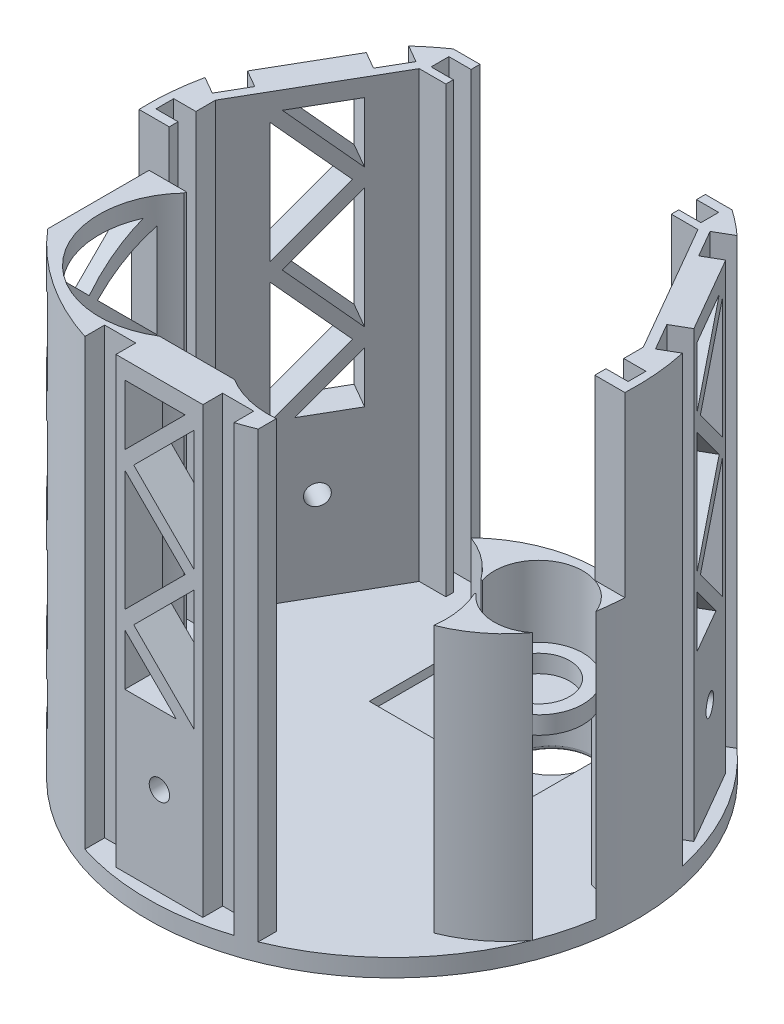
SolidWorks part; units mm, degrees
material "AISI Type 316L stainless steel"
ref_plane "Front Plane" through (0, 0, 0) normal (0, 0, 1) x (1, 0, 0)
ref_plane "Top Plane" through (0, 0, 0) normal (0, 1, 0) x (1, 0, 0)
ref_plane "Right Plane" through (0, 0, 0) normal (1, 0, 0) x (0, 0, -1)
other "Center of Mass"
sketch "Sketch1" plane through (0, 0, 0) normal (0, 1, 0) x (1, 0, 0)
  line L0 (0, 0) -> (0, -30.5) construction
  line L1 (-7.894, -24.4607) -> (-5.394, -24.4607)
  line L2 (0, 0) -> (-7.894, -29.4607) construction
  line L3 (-7.894, -29.4607) -> (7.894, -29.4607) construction
  line L4 (7.894, -29.4607) -> (7.894, -24.4607)
  line L5 (-7.894, -29.4607) -> (-7.894, -24.4607)
  line L6 (7.894, -24.4607) -> (5.394, -24.4607)
  line L7 (-5.394, -24.4607) -> (-5.394, -27.9849)
  line L8 (-8.394, -26.1876) -> (8.394, -26.1876) construction
  line L9 (5.394, -27.9849) -> (5.394, -24.4607)
  line L10 (5.394, -24.4607) -> (5.5317, -24.5711)
  line L11 (-8.394, -26.1876) -> (-8.394, -23.9607)
  line L12 (-8.394, -23.9607) -> (-4.894, -23.9607)
  line L13 (-4.894, -23.9607) -> (-4.894, -26.1876)
  line L14 (4.894, -26.1876) -> (4.894, -23.9607)
  line L15 (4.894, -23.9607) -> (8.394, -23.9607)
  line L16 (8.394, -23.9607) -> (8.394, -26.1876)
  line L17 (-4.8497, -26.1876) -> (4.9382, -26.1876)
  line L18 (-20.2543, 17.2938) -> (-25.1482, 8.8172)
  line L19 (-18.3036, 16.2187) -> (-20.2321, 17.3321)
  line L20 (-25.1261, 8.8555) -> (-23.1976, 7.7421)
  line L21 (-23.1976, 7.7421) -> (-24.9476, 4.711)
  line L22 (-24.9476, 4.711) -> (-26.8761, 5.8244)
  line L23 (-16.5536, 19.2498) -> (-18.3036, 16.2187)
  line L24 (-18.4821, 20.3632) -> (-16.5536, 19.2498)
  line L25 (25.104, 8.8938) -> (20.21, 17.3704)
  line L26 (23.1976, 7.7421) -> (25.1261, 8.8555)
  line L27 (20.2321, 17.3321) -> (18.3036, 16.2187)
  line L28 (18.3036, 16.2187) -> (16.5536, 19.2498)
  line L29 (16.5536, 19.2498) -> (18.4821, 20.3632)
  line L30 (24.9476, 4.711) -> (23.1976, 7.7421)
  line L31 (24.9476, 4.711) -> (26.8761, 5.8244)
  line L32 (0, 0) -> (-30.5, 0) construction
  line L33 (0, 0) -> (30.5, 0) construction
  line L34 (-24.0816, 4.211) -> (-15.6876, 18.7498)
  line L35 (-24.0816, 4.211) -> (-24.0816, -1)
  line L36 (-24.0816, -1) -> (-27.4818, -1)
  line L37 (15.6876, 18.7498) -> (24.0816, 4.211)
  line L38 (-24.0816, 0) -> (-26.5816, 0)
  line L39 (-24.0816, 0) -> (-24.0816, 2)
  line L40 (-24.0816, 2) -> (-26.5816, 2)
  line L41 (-26.5816, 0) -> (-26.5816, 2)
  line L42 (24.0816, 4.211) -> (24.0816, -1)
  line L43 (24.0816, -1) -> (27.4818, -1)
  line L44 (10.394, -25.4601) -> (10.394, -23.4207)
  line L45 (24.0816, 0) -> (26.5816, 0)
  line L46 (24.0816, 0) -> (24.0816, 2)
  line L47 (24.0816, 2) -> (26.5816, 2)
  line L48 (26.5816, 0) -> (26.5816, 2)
  line L49 (-15.6876, 18.7498) -> (-12.6876, 18.7498)
  line L50 (-15.6876, 18.7498) -> (-15.6876, 22.5865)
  line L51 (-15.6876, 22.5865) -> (-12.6876, 22.5865)
  line L52 (-12.6876, 18.7498) -> (-12.6876, 22.5865)
  line L53 (-12.6876, 19.5865) -> (-15.1876, 19.5865)
  line L54 (-12.6876, 19.5865) -> (-12.6876, 21.5865)
  line L55 (-12.6876, 21.5865) -> (-15.1876, 21.5865)
  line L56 (-15.1876, 19.5865) -> (-15.1876, 21.5865)
  line L57 (15.6876, 18.7498) -> (12.6876, 18.7498)
  line L58 (15.6876, 18.7498) -> (15.6876, 22.5865)
  line L59 (15.6876, 22.5865) -> (12.6876, 22.5865)
  line L60 (12.6876, 18.7498) -> (12.6876, 22.5865)
  line L61 (12.6876, 21.5865) -> (15.1876, 21.5865)
  line L62 (12.6876, 21.5865) -> (12.6876, 19.5865)
  line L63 (12.6876, 19.5865) -> (15.1876, 19.5865)
  line L64 (15.1876, 21.5865) -> (15.1876, 19.5865)
  line L65 (-10.394, -25.4601) -> (-10.394, -23.4207)
  line L66 (-4.2322, -21.9607) -> (4.2322, -21.9607)
  line L67 (26.8761, 5.8244) -> (24.9476, 4.711) [skipped]
  line L68 (25.104, 8.8938) -> (25.1261, 8.8555)
  line L69 (-20.2543, 17.2938) -> (-20.2321, 17.3321)
  line L70 (-4.8497, -26.1876) -> (-4.894, -26.1876)
  line L71 (-16.5536, -6.3723) -> (-26.7515, -6.3723)
  line L72 (-20.981, -17.7777) -> (-20.981, -6.3723)
  line L73 (-16.7944, -6.3723) -> (-16.7944, -6.6203)
  line L74 (17.6273, -7.6343) -> (17.7595, -7.5899)
  line L75 (18.6043, -9.3242) -> (18.6965, -9.2455)
  circle A0 centre (0, 0) radius 27.5
  circle A1 centre (0, 0) radius 28.5
  circle A2 centre (0, 0) radius 30.5
  circle A3 centre (9.5, -13.4607) radius 10
  circle A4 centre (-9.5, -13.4607) radius 10
  circle A5 centre (22.5, -6) radius 5
  arc A6 (24.0816, 0) -> (12.9668, -4.0809) centre (23.1976, -14.7689) ccw
  arc A7 (25.6686, -9.8678) -> (19.4225, -14.7031) centre (14.1755, -1.4732) cw
  point P25 (-24.0816, 4.211)
  point P48 (0, 0)
  point P49 (-15.6876, 18.7498)
  point P52 (-24.0816, 0)
  point P59 (24.0816, 4.211)
  point P60 (15.6876, 18.7498)
  point P63 (24.0816, 0)
  point P70 (25.3316, 2)
  point P105 (24.0816, -8.2391)
  dimension "D1" = 55
  dimension "D2" = 57
  dimension "D3" = 61
  dimension "D36" = 9.5
  dimension "D37" = 9.5
  dimension "D38" = 0
  dimension "D41" = 20
  dimension "D42" = 20
  dimension "D22" = 10
  dimension "D4" = 2.5
  dimension "D5" = 15
  dimension "D6" = 5
  dimension "D7" = 5
  dimension "D8" = 2.5
  dimension "D9" = 0.5
  dimension "D10" = 0.5
  dimension "D11" = 0.5
  dimension "D12" = 0.5
  dimension "D13" = 0.5
  dimension "D15" = 1
  dimension "D16" = 0
  dimension "D17" = 0
  dimension "D18" = 1
  dimension "D19" = 1
  dimension "D20" = 2.5
  dimension "D21" = 2
  dimension "D23" = 1
  dimension "D24" = 0
  dimension "D25" = 1
  dimension "D26" = 1
  dimension "D27" = 2.5
  dimension "D28" = 2
  dimension "D29" = 27.5
  dimension "D30" = 3
  dimension "D31" = 2
  dimension "D32" = 2.5
  dimension "D33" = 1
  dimension "D34" = 3
  dimension "D35" = 2.5
  dimension "D39" = 10.5
  dimension "D40" = 2
  dimension "D43" = 2
  dimension "D44" = 2
  dimension "D45" = 5
  dimension "D46" = 22.5
  dimension "D14" = 3
extrude "Boss-Extrude1" add sketch "Sketch1" along normal blind 50 contours L50 A0 L24 L23 L19 L69 L18 L20 L21 L22 L36 L35 L38 L41 L40 L34 | L53 L56 L55 L52 L51 L50 L49 | L43 A0 L31 L30 L26 L68 L25 L27 L28 L29 L58 L37 L42 L47 L48 L45 | L61 L64 L63 L60 L57 L58 L59 | A4 L65 A0 L11 L12 L13 L70 L17 L14 L15 L16 L44 A3 L66 | A4 L71 A0 L65 | L42 A6 A3 A5 A0 L43 | A7 A5 A3 region at (0, 0, 24.1018) region at (-16.0227, 0, 22.0809) region at (-21.9077, 0, -10.4758) region at (21.2944, 0, 12.0214) region at (20.7612, 0, 1.1374) region at (21.9077, 0, -10.4758) region at (-14.1876, 0, -22.5378) region at (15.6389, 0, -20.6681)
sketch "Sketch3" plane through (-19.8846, 0, -11.4804) normal (0.866, 0, 0.5) x (0.5, 0, -0.866)
  line L0 (-8.394, 0) -> (8.394, 0) construction
  circle A0 centre (0, 10) radius 1.15
  dimension "D1" = 10
  dimension "D2" = 2.3
extrude "Cut-Extrude1" cut sketch "Sketch3" against normal blind 5
sketch "Sketch4" plane through (-19.8846, 0, -11.4804) normal (0.866, 0, 0.5) x (0.5, 0, -0.866)
  line L0 (-8.394, 50) -> (8.394, 50) construction
  line L1 (-3.894, 48) -> (3.894, 48)
  line L2 (-3.894, 48) -> (-3.894, 14)
  line L3 (-3.894, 14) -> (3.894, 14)
  line L4 (3.894, 48) -> (3.894, 14)
  line L7 (-2.894, 48) -> (3.894, 41.212)
  line L8 (-3.894, 47) -> (3.894, 39.212)
  line L9 (-3.894, 47) -> (-3.894, 48)
  line L10 (3.894, 41.212) -> (-3.894, 33.4241)
  line L11 (-3.894, 33.4241) -> (3.894, 25.6361)
  line L12 (3.894, 25.6361) -> (-3.894, 17.8482)
  line L13 (-3.894, 17.8482) -> (0, 14)
  line L14 (3.894, 39.212) -> (-2.894, 32.4241)
  line L15 (-2.894, 32.4241) -> (-3.894, 31.4241)
  line L16 (-3.894, 31.4241) -> (3.894, 23.6361)
  line L17 (3.894, 23.6361) -> (-3.894, 15.8482)
  line L18 (-3.894, 17.8482) -> (3.894, 17.8482)
  circle A0 centre (0, 10) radius 1.15 construction
  dimension "D1" = 4
  dimension "D2" = 2
  dimension "D3" = 1
  dimension "D4" = 1
  dimension "D5" = 45
  dimension "D6" = 180
  dimension "D7" = 1
  dimension "D8" = 1
extrude "Cut-Extrude2" cut sketch "Sketch4" against normal blind 5 contours L10 L8 L2 | L1 L7 L4 | L4 L14 L11 | L16 L2 L12 | L17 L18 L4 region at (-19.0689, 45.7373, -12.8931) region at (-20.7002, 40.212, -10.0676) region at (-19.0689, 32.4241, -12.8931) region at (-20.7002, 24.6361, -10.0676) region at (-18.9023, 19.7775, -13.1818)
sketch "Sketch5" plane through (19.8846, 0, -11.4804) normal (-0.866, 0, 0.5) x (0.5, 0, 0.866)
  line L0 (-8.394, 0) -> (8.394, 0) construction
  line L1 (-8.394, 50) -> (8.394, 50) construction
  line L2 (-3.894, 48) -> (3.894, 48)
  line L3 (-3.894, 48) -> (-3.894, 21.869)
  line L4 (-3.894, 21.869) -> (-3.894, 17.1313)
  line L5 (3.894, 48) -> (3.894, 21.869)
  line L6 (-2.894, 48) -> (3.894, 41.212)
  line L7 (-3.894, 47) -> (3.894, 39.212)
  line L8 (3.894, 41.212) -> (-3.894, 33.4241)
  line L9 (-3.894, 33.4241) -> (3.894, 25.6361)
  line L10 (3.894, 25.6361) -> (-3.894, 17.8482)
  line L11 (3.894, 39.212) -> (-3.894, 31.4241)
  line L12 (-3.894, 31.4241) -> (3.894, 23.6361)
  line L13 (3.894, 23.6361) -> (-2.6109, 17.1313)
  line L14 (-3.894, 17.1313) -> (3.894, 17.1313)
  line L15 (3.894, 17.1313) -> (3.894, 21.869)
  line L16 (-3.894, 17.8482) -> (3.894, 17.8482)
  circle A0 centre (0, 10) radius 1.15
  dimension "D1" = 2.3
  dimension "D2" = 10
  dimension "D3" = 1
  dimension "D4" = 1
  dimension "D5" = 2
  dimension "D6" = 1
  dimension "D7" = 1
  dimension "D8" = 45
  dimension "D9" = 180
extrude "Cut-Extrude3" cut sketch "Sketch5" against normal blind 5 contours L8 L7 L3 | L2 L6 L5 | L5 L11 L9 | L12 L3 L4 L10 | L13 L16 L15 L5 | A0 region at (20.7002, 45.7373, -10.0676) region at (19.0689, 40.212, -12.8931) region at (20.7002, 32.4241, -10.0676) region at (19.0689, 24.6361, -12.8931) region at (20.8669, 19.7775, -9.7789) region at (19.8846, 10, -11.4804)
sketch "Sketch6" plane through (0, 0, 21.9607) normal (0, 0, -1) x (-1, 0, 0)
  line L1 (4.2322, 0) -> (-4.2322, 0) construction
  circle A0 centre (0, 10) radius 1.15
  dimension "D7" = 2.3
  dimension "D1" = 10
extrude "Cut-Extrude5" cut sketch "Sketch6" against normal blind 10
sketch "Sketch7" plane through (0, 0, 21.9607) normal (0, 0, -1) x (-1, 0, 0)
  line L0 (4.2322, 50) -> (-4.2322, 50) construction
  line L1 (-3.894, 48) -> (3.894, 48)
  line L2 (-3.894, 48) -> (-3.894, 16.4949)
  line L3 (-3.894, 16.4949) -> (3.894, 16.4949)
  line L4 (3.894, 48) -> (3.894, 16.4949)
  line L5 (-2.894, 48) -> (3.894, 41.212)
  line L6 (-3.894, 47) -> (3.894, 39.212)
  line L7 (3.894, 41.212) -> (-3.894, 33.4241)
  line L8 (-3.894, 33.4241) -> (3.894, 25.6361)
  line L9 (3.894, 25.6361) -> (-3.894, 17.8482)
  line L10 (3.894, 39.212) -> (-3.894, 31.4241)
  line L11 (-3.894, 31.4241) -> (3.894, 23.6361)
  line L12 (3.894, 23.6361) -> (-3.2472, 16.4949)
  line L13 (-3.894, 17.8482) -> (3.894, 17.8482)
  dimension "D1" = 2
  dimension "D2" = 1
  dimension "D3" = 1
  dimension "D4" = 1
  dimension "D5" = 45
  dimension "D6" = 1
  dimension "D7" = 180
extrude "Cut-Extrude6" cut sketch "Sketch7" against normal blind 5 contours L1 L5 L4 | L7 L6 L2 | L4 L10 L8 | L11 L2 L9 | L12 L13 L4 region at (-1.6313, 45.7373, 21.9607) region at (1.6313, 40.212, 21.9607) region at (-1.6313, 32.4241, 21.9607) region at (1.6313, 24.6361, 21.9607) region at (-1.9647, 19.7775, 21.9607)
sketch "Sketch8" plane through (0, 0, 0) normal (0, -1, 0) x (-1, 0, 0)
  circle A0 centre (0, 0) radius 27.5
extrude "Boss-Extrude3" add sketch "Sketch8" along normal blind 2
sketch "Sketch9" plane through (0, 0, 0) normal (0, 1, 0) x (1, 0, 0)
  line L0 (12.6876, 18.7498) -> (-12.6876, 18.7498) construction
  line L1 (24.0816, 2) -> (-24.0816, 2) construction
  line L3 (11.6876, 18.7498) -> (-6.8124, 18.7498)
  line L4 (11.6876, 18.7498) -> (11.6876, 4.2498)
  line L5 (11.6876, 4.2498) -> (-6.8124, 4.2498)
  line L6 (-6.8124, 18.7498) -> (-6.8124, 4.2498)
  dimension "D1" = 18.5
  dimension "D2" = 14.5
  dimension "D3" = 0
  dimension "D4" = 1
extrude "Cut-Extrude7" cut sketch "Sketch9" against normal blind 1
sketch "Sketch10" plane through (0, -1, 0) normal (0, 1, 0) x (1, 0, 0)
  line L0 (11.6876, 4.2498) -> (11.6876, 18.7498) construction
  circle A0 centre (6.4876, 11.4998) radius 4.5
  point P0 (11.6876, 11.4998)
  dimension "D1" = 5.2
  dimension "D2" = 9
extrude "Cut-Extrude8" cut sketch "Sketch10" against normal blind 5
sketch "Sketch11" plane through (0, 50, 0) normal (0, 1, 0) x (1, 0, 0)
  line L1 (11.3864, -8.2956) -> (24.0816, -8.2956)
  line L2 (11.3864, -8.2956) -> (11.3864, 1.6975)
  line L3 (11.3864, 1.6975) -> (24.0816, 1.6975)
  line L4 (24.0816, -8.2956) -> (24.0816, 1.6975)
extrude "Cut-Extrude13" cut sketch "Sketch11" against normal blind 20
sketch "Sketch12" plane through (0, 30, 0) normal (0, 1, 0) x (1, 0, 0)
  circle A0 centre (22.5, -6) radius 5
extrude "Boss-Extrude6" add sketch "Sketch12" against normal blind 10
sketch "Sketch13" plane through (0, 30, 0) normal (0, 1, 0) x (1, 0, 0)
  circle A0 centre (22.5, -6) radius 3.5
  arc A1 (17.7595, -7.5899) -> (18.6965, -9.2455) centre (22.5, -6) ccw construction
  dimension "D1" = 0
extrude "Cut-Extrude14" cut sketch "Sketch13" against normal blind 10
sketch "Sketch14" plane through (0, 50, 0) normal (0, 1, 0) x (1, 0, 0)
  line L1 (24.0816, -1.2567) -> (10.2974, -1.2567)
  line L2 (24.0816, -1.2567) -> (24.0816, -15.5662)
  line L3 (24.0816, -15.5662) -> (10.2974, -15.5662)
  line L4 (10.2974, -1.2567) -> (10.2974, -15.5662)
  line L5 (24.0816, -1.2567) -> (29.2907, -1.2567)
  line L6 (24.0816, -1.2567) -> (24.0816, -15.5662)
  line L7 (24.0816, -15.5662) -> (29.2907, -15.5662)
  line L8 (29.2907, -1.2567) -> (29.2907, -15.5662)
  arc M2 (24.0816, -1.2567) -> (27.1737, -4.2235) centre (22.5, -6) cw
  arc M3 (27.1737, -4.2235) -> (26.8761, 5.8244) centre (0, 0) ccw
extrude "Cut-Extrude15" cut sketch "Sketch14" against normal blind 20 contours L8 L5 L2 L7 M3 M2 | L1 L4 L3 L2 | L5 M2 M3 region at (17.1895, 50, 8.4115) region at (26.6987, 50, 8.7414) region at (26.4458, 50, 2.1236)
sketch "Sketch15" plane through (0, 30, 0) normal (0, 1, 0) x (1, 0, 0)
  circle A0 centre (22.5, -6) radius 5
  arc A1 (17.7595, -7.5899) -> (18.6965, -9.2455) centre (22.5, -6) ccw construction
  dimension "D1" = 0
  dimension "D2" = 0
extrude "Cut-Extrude17" cut sketch "Sketch15" against normal blind 8
sketch "Sketch16" plane through (-20.981, 0, 0) normal (-1, 0, 0) x (0, 0, 1)
  line L0 (6.3723, 50) -> (6.3723, 0) construction
  line L1 (8.3723, 48) -> (20.9607, 48)
  line L2 (8.3723, 48) -> (8.3723, 2)
  line L3 (8.3723, 2) -> (20.9607, 2)
  line L4 (20.9607, 48) -> (20.9607, 2)
  line L5 (17.7777, 50) -> (6.3723, 50) construction
  line L6 (9.3723, 48) -> (20.9607, 36.4115)
  line L7 (8.3723, 47) -> (20.9607, 34.4115)
  line L8 (20.9607, 36.4115) -> (8.3723, 23.823)
  line L9 (8.3723, 23.823) -> (20.9607, 11.2346)
  line L10 (20.9607, 11.2346) -> (11.7262, 2)
  line L11 (20.9607, 34.4115) -> (8.3723, 21.823)
  line L12 (8.3723, 21.823) -> (20.9607, 9.2346)
  line L13 (20.9607, 9.2346) -> (13.7262, 2)
  line L14 (19.9607, 48) -> (8.3723, 36.4115)
  line L15 (20.9607, 47) -> (8.3723, 34.4115)
  line L16 (8.3723, 34.4115) -> (20.9607, 21.823)
  line L17 (20.9607, 21.823) -> (8.3723, 9.2346)
  line L18 (8.3723, 9.2346) -> (15.6068, 2)
  line L19 (8.3723, 36.4115) -> (20.9607, 23.823)
  line L20 (20.9607, 23.823) -> (8.3723, 11.2346)
  line L21 (8.3723, 11.2346) -> (17.6068, 2)
  line L22 (15.6665, 3.9403) -> (20.9607, 3.9403)
  line L23 (20.9607, 3.9403) -> (8.3723, 3.9403)
  line M9 (17.7777, 0) -> (17.7777, 50)
  dimension "D1" = 2
  dimension "D2" = 2
  dimension "D3" = 1
  dimension "D4" = 2
  dimension "D5" = 1
  dimension "D6" = 45
  dimension "D7" = 1
  dimension "D8" = 45
  dimension "D9" = 1
  dimension "D10" = 45
extrude "Cut-Extrude18" cut sketch "Sketch16" against normal blind 8 contours L14 L7 L2 | L14 L1 L6 M9 | L14 L1 M9 | L4 L15 L6 M9 | L15 L6 M9 | L15 L19 L8 L7 M9 | L8 L7 M9 | L19 L4 L11 M9 | L11 L19 M9 | L20 L16 L11 L9 M9 | L16 L2 L8 | L20 L12 L2 | L4 L17 L9 M9 | L17 L9 M9 | L17 L21 L10 L12 M9 | L23 L18 L2 | L22 L4 L13 M9 | L13 L22 M9 | L12 L10 M9 | L20 L16 M9 region at (-20.981, 46.1389, 14.3098) region at (-20.981, 41.7058, 10.137) region at (-20.981, 47.2723, 18.5054) region at (-20.981, 41.7058, 17.074) region at (-20.981, 29.1173, 10.137) region at (-20.981, 35.4115, 14.3098) region at (-20.981, 41.7058, 19.5972) region at (-20.981, 35.4115, 18.5054) region at (-20.981, 16.5288, 10.137) region at (-20.981, 22.823, 14.3098) region at (-20.981, 29.1173, 17.074) region at (-20.981, 29.1173, 19.5972) region at (-20.981, 22.823, 18.5054) region at (-20.981, 5.7051, 10.137) region at (-20.981, 10.2346, 14.3098) region at (-20.981, 16.5288, 17.074) region at (-20.981, 16.5288, 19.5972) region at (-20.981, 10.2346, 18.5054) region at (-20.981, 4.6441, 17.074) region at (-20.981, 5.9057, 19.5972)
sketch "Sketch17" plane through (0, 0, 0) normal (0, 0, -1) x (-1, 0, 0)
  line L0 (-24.0816, 30) -> (-24.0816, 0) construction
  line L1 (-24.0816, 20) -> (-9.0816, 20)
  line L2 (-23.5816, 20) -> (-23.5816, 0)
  line L3 (-24.0816, 0) -> (-9.0816, 0)
  line L4 (-9.0816, 20) -> (-9.0816, 0)
  line L5 (-12.9668, 0) -> (-24.0816, 0) construction
  arc A0 (-20.0816, 20) -> (-9.0816, 9) centre (-10.0816, 19) cw
  arc A1 (-22.5816, 20) -> (-23.5816, 14) centre (-22.5816, 16.9167) ccw
  point P8 (-10.0816, 19)
  point P13 (-22.5816, 16.9167)
  dimension "D1" = 15
  dimension "D2" = 20
  dimension "D3" = 0
  dimension "D4" = 1
  dimension "D5" = 1
  dimension "D6" = 0.5
  dimension "D7" = 1
extrude "Cut-Extrude31" cut sketch "Sketch17" against normal blind 8 contours L1 A1 L2 L3 L4 A0 region at (16.3302, 9.9981, 0)
sketch "Sketch19" plane through (0, 0, 0) normal (0, 0, 1) x (1, 0, 0)
  line L1 (23.5816, 0) -> (22.3136, 0)
  line L2 (23.5816, 0) -> (23.5816, 20)
  line L3 (23.5816, 20) -> (22.3136, 20)
  line L4 (22.3136, 0) -> (22.3136, 20)
  arc A0 (22.5816, 20) -> (23.5816, 19) centre (22.5816, 19) cw
  point P6 (22.5816, 19)
  line M3 (22.3136, 0) -> (23.5816, 0)
  line M4 (23.5816, 0) -> (23.5816, 19.8333)
  arc M5 (23.5816, 19.8333) -> (22.5816, 20) centre (22.5816, 16.9167) ccw
  line M6 (22.5816, 20) -> (22.3136, 20)
  line M7 (22.3136, 20) -> (22.3136, 0)
  dimension "D1" = 1
  dimension "D2" = 1
extrude "Cut-Extrude32" cut sketch "Sketch19" against normal blind 1 contours M7 M3 M4 M5 M6 region at (22.9441, 9.9166, 0)
sketch "Sketch20" plane through (0, -2, 0) normal (0, -1, 0) x (-1, 0, 0)
  circle A0 centre (-6.4876, 11.4998) radius 4.5
  circle A1 centre (-6.4876, 11.4998) radius 4.5 construction
  circle A2 centre (-6.4876, 11.4998) radius 5.5
  dimension "D1" = 0
  dimension "D2" = 0
  dimension "D3" = 11
extrude "Boss-Extrude7" add sketch "Sketch20" along normal blind 3
fillet "Fillet1" radius 3 1 edges at (6.4876, -2, -16.9998)
fillet "Fillet2" radius 0.5 2 edges at (6.4876, -5, -15.9998) (6.4876, -5, -16.9998)
